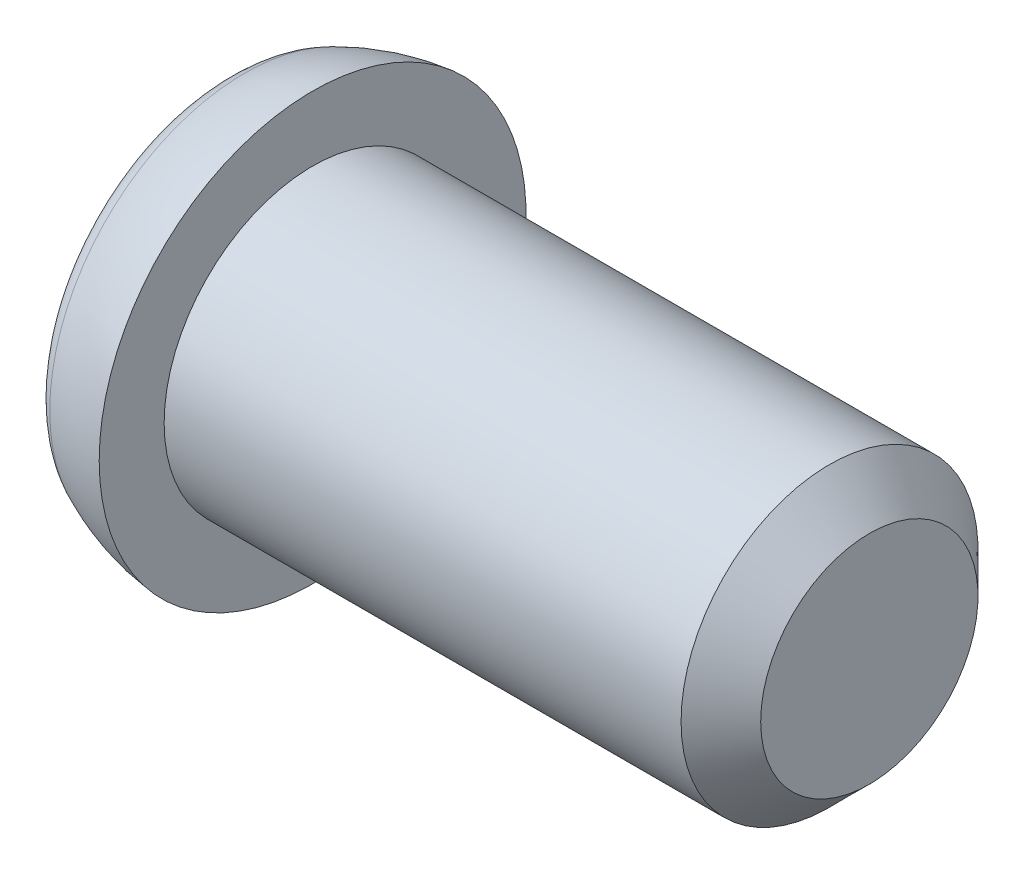
SolidWorks part; units mm, degrees
ref_plane "Front Plane" through (0, 0, 0) normal (0, 0, 1) x (1, 0, 0)
ref_plane "Top Plane" through (0, 0, 0) normal (0, 1, 0) x (1, 0, 0)
ref_plane "Right Plane" through (0, 0, 0) normal (1, 0, 0) x (0, 0, -1)
ref_plane "Plane1" through (0, 0, 0) normal (0, 0, 1) x (1, 0, 0)
sketch "Sketch1" plane through (0, 0, 0) normal (0, 0, 1) x (1, 0, 0)
  line L0 (-0.5, 0) -> (-0.5, 0.8413)
  line L1 (0, 1.15) -> (0, 0.8)
  line L2 (0, 0.8) -> (2.7855, 0.8)
  line L3 (2.7855, 0.8) -> (3, 0.5855)
  line L4 (3, 0.5855) -> (3, 0)
  line L5 (3, 0) -> (-0.5, 0)
  line L6 (3, 0) -> (-0.5, 0) construction
  arc A0 (-0.5, 0.8413) -> (-0.3663, 1.0502) centre (-0.27, 0.8413) cw
  arc A1 (-0.3663, 1.0502) -> (0, 1.15) centre (0.115, 0.0058) cw
revolve "Revolve1" add sketch "Sketch1" angle 360 about L6 reverse direction yes
cosmetic thread "Cosmetic Thread1" parameters "D1"=2.6276, "D2"=1.171
ref_plane "Plane2" through (0, 0, 0) normal (0, 0, 1) x (1, 0, 0)
sketch "Sketch2" plane through (0, 0, 0) normal (0, 0, 1) x (1, 0, 0)
  line L0 (-0.5, 0.575) -> (-0.5, -0.575)
  arc A0 (-0.5, -0.575) -> (0.2, 0) centre (-0.6583, 0.3313) ccw
  arc A1 (0.2, 0) -> (-0.5, 0.575) centre (-0.6583, -0.3313) ccw
extrude "Cut-Extrude1" cut sketch "Sketch2" against normal blind 0.115 and the other way blind 0.115
ref_plane "Plane3" through (0, 0, 0) normal (0, 1, 0) x (1, 0, 0)
sketch "Sketch3" plane through (0, 0, 0) normal (0, 1, 0) x (1, 0, 0)
  line L0 (-0.5, 0.575) -> (-0.5, -0.575)
  arc A0 (-0.5, -0.575) -> (0.2, 0) centre (-0.6583, 0.3313) ccw
  arc A1 (0.2, 0) -> (-0.5, 0.575) centre (-0.6583, -0.3313) ccw
extrude "Cut-Extrude2" cut sketch "Sketch3" against normal blind 0.115 and the other way blind 0.115
